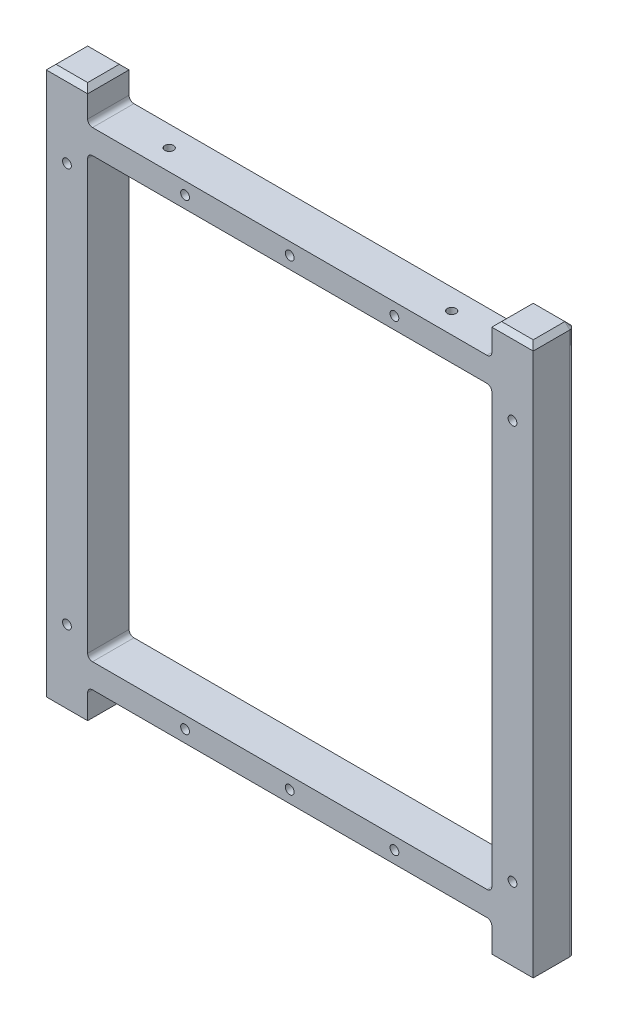
SolidWorks part; units mm, degrees
material "6061 Alloy"
ref_plane "Frontal" through (0, 0, 0) normal (0, 0, 1) x (1, 0, 0)
ref_plane "Superior" through (0, 0, 0) normal (0, 1, 0) x (1, 0, 0)
ref_plane "Direito" through (0, 0, 0) normal (1, 0, 0) x (0, 0, -1)
sketch "Sketch1" plane through (0, 0, 0) normal (0, 0, 1) x (1, 0, 0)
  line L1 (-50, -56.75) -> (50, -56.75)
  line L2 (-50, -56.75) -> (-50, 56.75)
  line L3 (-50, 56.75) -> (50, 56.75)
  line L4 (50, -56.75) -> (50, 56.75)
  line L5 (-50, -56.75) -> (50, 56.75) construction
  line L6 (-50, 56.75) -> (50, -56.75) construction
  point P0 (0, 0)
  dimension "D1" = 113.5
  dimension "D2" = 100
extrude "Boss-Extrude1" add sketch "Sketch1" along normal mid plane 8.5
sketch "Sketch4" plane through (0, 0, 4.25) normal (0, 0, 1) x (1, 0, 0)
  line L0 (-50, 56.75) -> (-50, -56.75) construction
  line L1 (-40.5, -44.75) -> (40.5, -44.75)
  line L2 (-41.5, -43.75) -> (-41.5, 44.25)
  line L3 (-40.5, 45.25) -> (40.5, 45.25)
  line L4 (41.5, -43.75) -> (41.5, 44.25)
  line L5 (-40.5, -43.75) -> (40.5, 44.25) construction
  line L6 (-40.5, 44.25) -> (40.5, -43.75) construction
  line L7 (50, 56.75) -> (-50, 56.75) construction
  line L8 (-41.5, 56.75) -> (41.5, 56.75)
  line L9 (-41.5, 56.75) -> (-41.5, 51.25)
  line L10 (-40.5, 50.25) -> (40.5, 50.25)
  line L11 (41.5, 56.75) -> (41.5, 51.25)
  line L12 (-50, -56.75) -> (50, -56.75) construction
  line L13 (-41.5, -56.75) -> (41.5, -56.75)
  line L14 (-41.5, -56.75) -> (-41.5, -50.75)
  line L15 (-40.5, -49.75) -> (40.5, -49.75)
  line L16 (41.5, -56.75) -> (41.5, -50.75)
  line L17 (50, -56.75) -> (50, 56.75) construction
  arc A0 (-41.5, 51.25) -> (-40.5, 50.25) centre (-40.5, 51.25) ccw
  arc A1 (40.5, 50.25) -> (41.5, 51.25) centre (40.5, 51.25) ccw
  arc A2 (-40.5, 45.25) -> (-41.5, 44.25) centre (-40.5, 44.25) ccw
  arc A3 (40.5, 45.25) -> (41.5, 44.25) centre (40.5, 44.25) cw
  arc A4 (41.5, -43.75) -> (40.5, -44.75) centre (40.5, -43.75) cw
  arc A5 (-40.5, -44.75) -> (-41.5, -43.75) centre (-40.5, -43.75) cw
  arc A6 (-40.5, -49.75) -> (-41.5, -50.75) centre (-40.5, -50.75) ccw
  arc A7 (40.5, -49.75) -> (41.5, -50.75) centre (40.5, -50.75) cw
  point P0 (1.8681, -1.8902)
  dimension "D11" = 1
  dimension "D12" = 1
  dimension "D13" = 1
  dimension "D14" = 1
  dimension "D15" = 1
  dimension "D16" = 1
  dimension "D17" = 1
  dimension "D18" = 1
  dimension "D1" = 8.5
  dimension "D2" = 8.5
  dimension "D3" = 8.5
  dimension "D4" = 6.5
  dimension "D5" = 8.5
  dimension "D6" = 8.5
  dimension "D7" = 7
  dimension "D8" = 5
  dimension "D9" = 5
  dimension "D10" = 8.5
extrude "Cut-Extrude1" cut sketch "Sketch4" against normal through all
hole_wizard "M1.6 Hole1-IntUnion" positions "Sketch6" profile "Sketch5" hole size "M1.6" standard "DIN"
sketch "Sketch6" plane through (0, 0, 4.25) normal (0, 0, 1) x (1, 0, 0)
  line L0 (-50, 56.75) -> (-50, -56.75) construction
  line L1 (50, -56.75) -> (50, 56.75) construction
  line L2 (-40.5, 50.25) -> (40.5, 50.25) construction
  line L3 (40.5, -49.75) -> (-40.5, -49.75) construction
  point P0 (-45.75, -40.75)
  point P2 (45.75, -40.75)
  point P4 (-45.75, 41.25)
  point P6 (45.75, 41.25)
  dimension "D1" = 4.25
  dimension "D2" = 4.25
  dimension "D3" = 9
  dimension "D4" = 9
sketch "Sketch5" plane through (-45.75, -40.75, 4.25) normal (1, 0, 0) x (0, -1, 0)
  line L0 (0, 0) -> (0, 5.5408)
  line L1 (0, 5.5408) -> (0.9, 5)
  line L2 (0.9, 5) -> (0.9, 0)
  line L5 (0.9, 0) -> (0, 0)
  line L10 (0, 5.5408) -> (-0.9, 5) construction
  line L11 (0, -6.35) -> (0, 107.95) construction
  dimension "Hole Dia." = 1.8
  dimension "Hole Depth" = 5
  dimension "Drill Angle" = 118
hole_wizard "M1.6 Hole2-IntUnionPlate" positions "Sketch19" profile "Sketch18" countersink size "M1.6" standard "DIN" end condition through all
sketch "Sketch19" plane through (0, 0, -4.25) normal (0, 0, -1) x (-1, 0, 0)
  line L0 (-41.5, 51.25) -> (-41.5, 56.75) construction
  line L1 (41.5, 56.75) -> (41.5, 51.25) construction
  line L2 (40.5, 50.25) -> (-40.5, 50.25) construction
  line L3 (-40.5, -49.75) -> (40.5, -49.75) construction
  point P0 (-21.5, 47.75)
  point P2 (21.5, 47.75)
  point P4 (-21.5, -47.25)
  point P6 (21.5, -47.25)
  dimension "D1" = 20
  dimension "D2" = 20
  dimension "D3" = 2.5
  dimension "D4" = 2.5
sketch "Sketch18" plane through (21.5, 47.75, -4.25) normal (1, 0, 0) x (0, 1, 0)
  line L0 (0, 0) -> (0, 8.5)
  line L1 (0, 8.5) -> (0.9, 8.5)
  line L2 (0.9, 8.5) -> (0.9, 0.9)
  line L3 (0.9, 0.9) -> (1.8, 0)
  line L5 (1.8, 0) -> (0, 0)
  line L6 (-0.9, 0.9) -> (-1.8, 0) construction
  line L11 (0, -6.35) -> (0, 107.95) construction
  dimension "Thru Hole Dia." = 1.8
  dimension "Thru Hole Depth" = 8.5
  dimension "Near C'Sink Dia." = 3.6
  dimension "Near C'Sink Angle" = 90
hole_wizard "M1.6 Hole3-ExtUnionSide" positions "Sketch21" profile "Sketch20" hole size "M1.6" standard "DIN"
sketch "Sketch21" plane through (0, 0, -4.25) normal (0, 0, -1) x (-1, 0, 0)
  line L0 (40.5, 50.25) -> (-40.5, 50.25) construction
  line L1 (-41.5, 51.25) -> (-41.5, 56.75) construction
  line L2 (41.5, 56.75) -> (41.5, 51.25) construction
  line L3 (-40.5, -49.75) -> (40.5, -49.75) construction
  point P0 (-35.5, 47.75)
  point P2 (35.5, 47.75)
  point P4 (-35.5, -47.25)
  point P6 (35.5, -47.25)
  dimension "D1" = 2.5
  dimension "D2" = 6
  dimension "D3" = 6
  dimension "D4" = 2.5
sketch "Sketch20" plane through (35.5, 47.75, -4.25) normal (1, 0, 0) x (0, 1, 0)
  line L0 (0, 0) -> (0, 3.5408)
  line L1 (0, 3.5408) -> (0.9, 3)
  line L2 (0.9, 3) -> (0.9, 0)
  line L5 (0.9, 0) -> (0, 0)
  line L10 (0, 3.5408) -> (-0.9, 3) construction
  line L11 (0, -6.35) -> (0, 107.95) construction
  dimension "Hole Dia." = 1.8
  dimension "Hole Depth" = 3
  dimension "Drill Angle" = 118
hole_wizard "M1.6 Hole4-IntUnionTop" positions "Sketch13" profile "Sketch12" hole size "M1.6" standard "DIN"
sketch "Sketch13" plane through (0, 0, 4.25) normal (0, 0, 1) x (1, 0, 0)
  line L0 (40.5, -49.75) -> (-40.5, -49.75) construction
  line L1 (-40.5, 50.25) -> (40.5, 50.25) construction
  point P0 (0, 47.75)
  point P2 (0, -47.25)
  dimension "D1" = 2.5
  dimension "D2" = 2.5
sketch "Sketch12" plane through (0, 47.75, 4.25) normal (1, 0, 0) x (0, -1, 0)
  line L0 (0, 0) -> (0, 3.5408)
  line L1 (0, 3.5408) -> (0.9, 3)
  line L2 (0.9, 3) -> (0.9, 0)
  line L5 (0.9, 0) -> (0, 0)
  line L10 (0, 3.5408) -> (-0.9, 3) construction
  line L11 (0, -6.35) -> (0, 107.95) construction
  dimension "Hole Dia." = 1.8
  dimension "Hole Depth" = 3
  dimension "Drill Angle" = 118
hole_wizard "M1.6 Hole5-ExtUnionTop" positions "Sketch23" profile "Sketch22" hole size "M1.6" standard "DIN"
sketch "Sketch23" plane through (0, 50.25, 0) normal (0, 1, 0) x (1, 0, 0)
  line L0 (-40.5, 4.25) -> (40.5, 4.25) construction
  line L1 (-41.5, 4.25) -> (-41.5, -4.25) construction
  line L2 (41.5, 4.25) -> (41.5, -4.25) construction
  point P0 (-29, 0)
  point P2 (29, 0)
  dimension "D1" = 4.25
  dimension "D2" = 12.5
  dimension "D3" = 12.5
sketch "Sketch22" plane through (-29, 50.25, 0) normal (1, 0, 0) x (0, 0, 1)
  line L0 (0, 0) -> (0, 2.5408)
  line L1 (0, 2.5408) -> (0.9, 2)
  line L2 (0.9, 2) -> (0.9, 0)
  line L5 (0.9, 0) -> (0, 0)
  line L10 (0, 2.5408) -> (-0.9, 2) construction
  line L11 (0, -6.35) -> (0, 107.95) construction
  dimension "Hole Dia." = 1.8
  dimension "Hole Depth" = 2
  dimension "Drill Angle" = 118
hole_wizard "M1.6 Hole6-ExtUnionTop" positions "Sketch17" profile "Sketch16" hole size "M1.6" standard "DIN"
sketch "Sketch17" plane through (0, -49.75, 0) normal (0, -1, 0) x (-1, 0, 0)
  line L0 (41.5, 4.25) -> (41.5, -4.25) construction
  line L1 (-41.5, 4.25) -> (-41.5, -4.25) construction
  line L2 (-40.5, -4.25) -> (40.5, -4.25) construction
  point P0 (29, 0)
  point P2 (-29, 0)
  dimension "D1" = 12.5
  dimension "D2" = 12.5
  dimension "D3" = 4.25
sketch "Sketch16" plane through (-29, -49.75, 0) normal (1, 0, 0) x (0, 0, -1)
  line L0 (0, 0) -> (0, 3.5408)
  line L1 (0, 3.5408) -> (0.9, 3)
  line L2 (0.9, 3) -> (0.9, 0)
  line L5 (0.9, 0) -> (0, 0)
  line L10 (0, 3.5408) -> (-0.9, 3) construction
  line L11 (0, -6.35) -> (0, 107.95) construction
  dimension "Hole Dia." = 1.8
  dimension "Hole Depth" = 3
  dimension "Drill Angle" = 118
fillet "Fillet1" radius 1 2 edges at (-50, 0, -4.25) (50, 0, -4.25)
chamfer "Chamfer1" distance 1 angle 45 20 edges at (-41.5, -56.75, 0) (-45.75, -56.75, 4.25) (-50, -56.75, 0.5) (-49.7071, -56.75, -3.9571) (-45.25, -56.75, -4.25) (-45.75, 56.75, 4.25) (-50, 56.75, 0.5) (-49.7071, 56.75, -3.9571) (-45.25, 56.75, -4.25) (-41.5, 56.75, 0) (45.75, -56.75, 4.25) (41.5, -56.75, 0) (45.25, -56.75, -4.25) (49.7071, -56.75, -3.9571) (50, -56.75, 0.5) (49.7071, 56.75, -3.9571) (50, 56.75, 0.5) (45.75, 56.75, 4.25) (41.5, 56.75, 0) (45.25, 56.75, -4.25)
